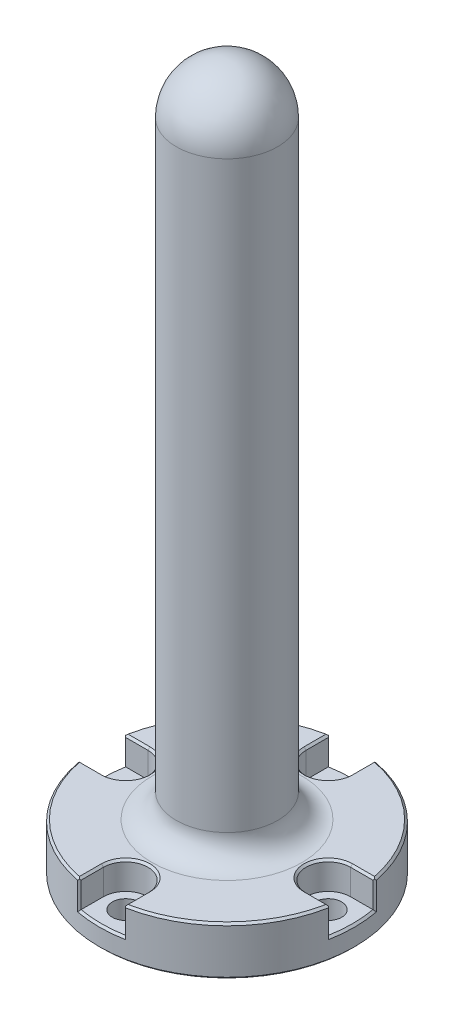
SolidWorks part; units mm, degrees
ref_plane "前视基准面" through (0, 0, 0) normal (0, 0, 1) x (1, 0, 0)
ref_plane "上视基准面" through (0, 0, 0) normal (0, 1, 0) x (1, 0, 0)
ref_plane "右视基准面" through (0, 0, 0) normal (1, 0, 0) x (0, 0, -1)
sketch "草图1" plane through (0, 0, 0) normal (0, 1, 0) x (1, 0, 0)
  circle A0 centre (0, 0) radius 31.5
  dimension "D1" = 63
extrude "凸台-拉伸1" add sketch "草图1" along normal blind 12
sketch "草图2" plane through (0, 12, 0) normal (0, 1, 0) x (1, 0, 0)
  line L0 (0, 0) -> (0, 25) construction
  circle A0 centre (0, 0) radius 25 construction
  dimension "D1" = 50
hole_wizard "打孔尺寸(%根据)内六角圆柱头螺钉的类型5" positions "草图13" profile "草图14" counterbore size "M6" standard "GB" end condition through all
sketch "草图13" plane through (0, 12, 0) normal (0, 1, 0) x (1, 0, 0)
  point P0 (0, 25)
sketch "草图14" plane through (0, 12, -25) normal (1, 0, 0) x (0, 0, 1)
  line L0 (0, 0) -> (0, 12)
  line L1 (0, 12) -> (3.3, 12)
  line L3 (3.3, 12) -> (3.3, 6.8)
  line L4 (3.3, 6.8) -> (5.5, 6.8)
  line L5 (5.5, 6.8) -> (5.5, 0)
  line L7 (5.5, 0) -> (0, 0)
  line L11 (0, -6.35) -> (0, 107.95) construction
  dimension "通孔孔直径" = 6.6
  dimension "通孔孔深度" = 12
  dimension "柱形沉头孔直径" = 11
  dimension "柱形沉头孔深度" = 6.8
pattern_circular "阵列(圆周)2" count 4 over 360 about axis through (0, 12, 0) along (0, -1, 0) of "打孔尺寸(%根据)内六角圆柱头螺钉的类型5"
chamfer "倒角2" distance 0.5 angle 45 2 edges at (0, 0, 31.5) (0, 12, 31.5)
sketch "草图15" plane through (0, 12, 0) normal (0, 1, 0) x (1, 0, 0)
  circle A0 centre (0, 0) radius 12.5
  dimension "D1" = 25
extrude "凸台-拉伸2" add sketch "草图15" along normal blind 150
fillet "圆角2" radius 6 1 edges at (0, 12, 12.5)
sketch "草图17" plane through (0, 0, 0) normal (0, 0, 1) x (1, 0, 0)
  line L0 (0, 0) -> (0, 162) construction
  line L1 (-12.5, 162) -> (12.5, 162)
  arc A0 (12.5, 162) -> (-12.5, 162) centre (0, 162) ccw
  dimension "D2" = 25
  dimension "D1" = 162
revolve "旋转5" add sketch "草图17" angle 360 about L1
sketch "草图18" plane through (0, 12, 0) normal (0, 1, 0) x (1, 0, 0)
  line L0 (5.5, 25) -> (5.5, 35)
  line L1 (5.5, 35) -> (-5.5, 35)
  line L2 (-5.5, 35) -> (-5.5, 25)
  line L3 (-5.5, 25) -> (5.5, 25)
  line L4 (35, 5.5) -> (25, 5.5)
  line L5 (35, -5.5) -> (35, 5.5)
  line L6 (25, -5.5) -> (35, -5.5)
  line L7 (25, 5.5) -> (25, -5.5)
  line L8 (5.5, -35) -> (5.5, -25)
  line L9 (-5.5, -35) -> (5.5, -35)
  line L10 (-5.5, -25) -> (-5.5, -35)
  line L11 (5.5, -25) -> (-5.5, -25)
  line L12 (-35, -5.5) -> (-25, -5.5)
  line L13 (-35, 5.5) -> (-35, -5.5)
  line L14 (-25, 5.5) -> (-35, 5.5)
  line L15 (-25, -5.5) -> (-25, 5.5)
  circle A0 centre (0, 25) radius 5.5 construction
  circle A1 centre (0, 25) radius 5.5 construction
  dimension "D1" = 11
  dimension "D2" = 10
  dimension "D3" = 4
extrude "切除-拉伸1" cut sketch "草图18" against normal blind 6.8
chamfer "倒角3" distance 0.5 angle 45 24 edges at (0, 5.2, -31.5) (5.5, 12, -27.7541) (0, 12, -19.5) (-5.5, 12, -27.7541) (5.5, 8.35, -31.0161) (-5.5, 8.35, -31.0161) (31.5, 5.2, 0) (31.0161, 8.35, 5.5) (31.0161, 8.35, -5.5) (27.7541, 12, 5.5) (19.5, 12, 0) (27.7541, 12, -5.5) (5.5, 8.35, 31.0161) (0, 5.2, 31.5) (-5.5, 8.35, 31.0161) (5.5, 12, 27.7541) (-5.5, 12, 27.7541) (0, 12, 19.5) (-31.0161, 8.35, 5.5) (-31.5, 5.2, 0) (-31.0161, 8.35, -5.5) (-27.7541, 12, 5.5) (-19.5, 12, 0) (-27.7541, 12, -5.5) first distance on face at (0, 5.2, -21.7) first distance on face at (0, 12, 0) first distance on face at (5.5, 9.23, -28.4573) first distance on face at (-5.5, 9.13, -28.5589) first distance on face at (21.7, 5.2, 0) first distance on face at (28.4573, 9.23, 5.5) first distance on face at (28.5589, 9.13, -5.5) first distance on face at (5.5, 9.13, 28.5589) first distance on face at (0, 5.2, 21.7) first distance on face at (-5.5, 9.23, 28.4573) first distance on face at (-28.5589, 9.13, 5.5) first distance on face at (-21.7, 5.2, 0) first distance on face at (-28.4573, 9.23, -5.5)
